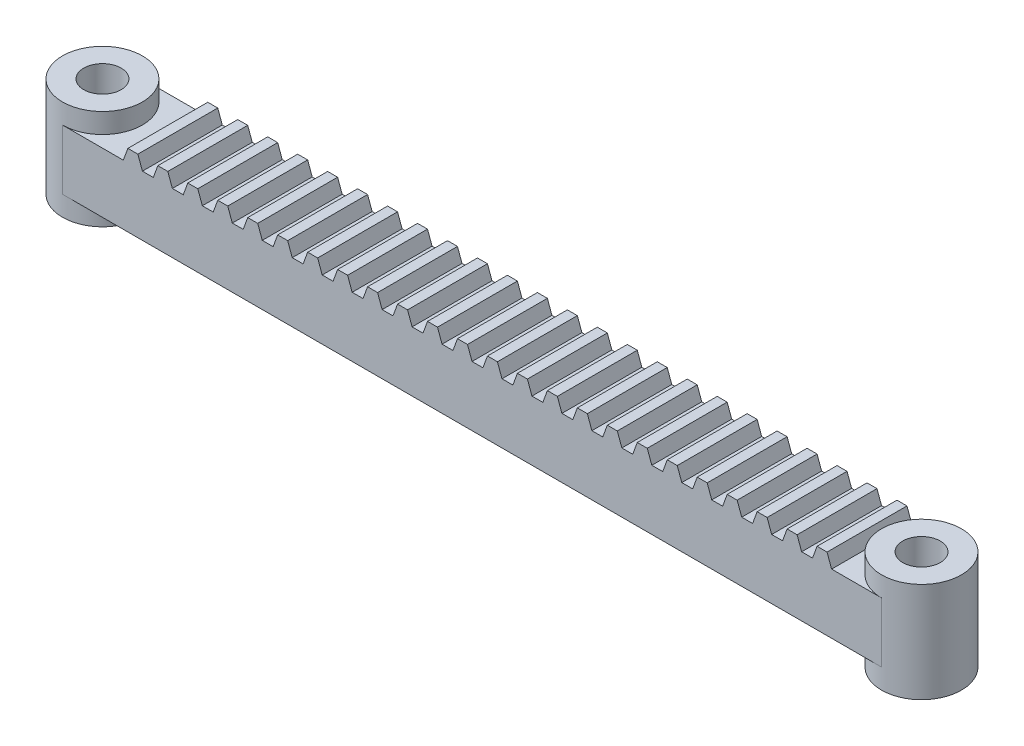
SolidWorks part; units mm, degrees
material "Galvanized Steel"
ref_plane "Front Plane" through (0, 0, 0) normal (0, 0, 1) x (1, 0, 0)
ref_plane "Top Plane" through (0, 0, 0) normal (0, 1, 0) x (1, 0, 0)
ref_plane "Right Plane" through (0, 0, 0) normal (1, 0, 0) x (0, 0, -1)
sketch "Sketch1" plane through (0, 0, 0) normal (0, 1, 0) x (1, 0, 0)
  line L0 (0, 0) -> (164, 0) construction
  line L1 (0, 8) -> (164, 8)
  line L2 (0, -8) -> (164, -8)
  arc A0 (0, 8) -> (0, -8) centre (0, 0) ccw
  arc A1 (164, -8) -> (164, 8) centre (164, 0) ccw
  circle A2 centre (0, 0) radius 3.75
  circle A3 centre (164, 0) radius 3.75
  circle A4 centre (0, 0) radius 8
  circle A5 centre (164, 0) radius 8
  point P3 (82, 0)
  dimension "D3" = 7.5
  dimension "D1" = 164
  dimension "D2" = 16
extrude "Boss-Extrude1" add sketch "Sketch1" along normal mid plane 20 contours A2 A4 A0 | A1 A5 A3 region at (5.4969, 0, -5.4969) region at (169.4969, 0, -5.4969)
extrude "Boss-Extrude2" add sketch "Sketch1<3>" along normal mid plane 12 contours L0 A4 L2 A5 | A4 L0 A5 L1 region at (82, 0, -4.0502) region at (82, 0, 4.0502)
sketch "Sketch1<3>" plane through (0, 0, 0) normal (0, 1, 0) x (1, 0, 0) same geometry as "Sketch1"
sketch "Sketch2" plane through (0, 0, 8) normal (0, 0, 1) x (1, 0, 0)
  line L0 (154, 6) -> (153.0901, 8.5)
  line L1 (0, 6) -> (164, 6) construction
  line L2 (153.0901, 8.5) -> (151.0901, 8.5)
  line L3 (151.0901, 8.5) -> (150.1801, 6)
  line L4 (172, -10) -> (172, 10) construction
  line L5 (150.1801, 6) -> (154, 6)
  dimension "D1" = 18
  dimension "D2" = 40
  dimension "D3" = 2
  dimension "D4" = 2.5
extrude "Boss-Extrude3" add sketch "Sketch2" against normal blind 16
pattern_linear "LPattern1" count 24 spacing 6 along (-1, 0, 0) of "Boss-Extrude3"
